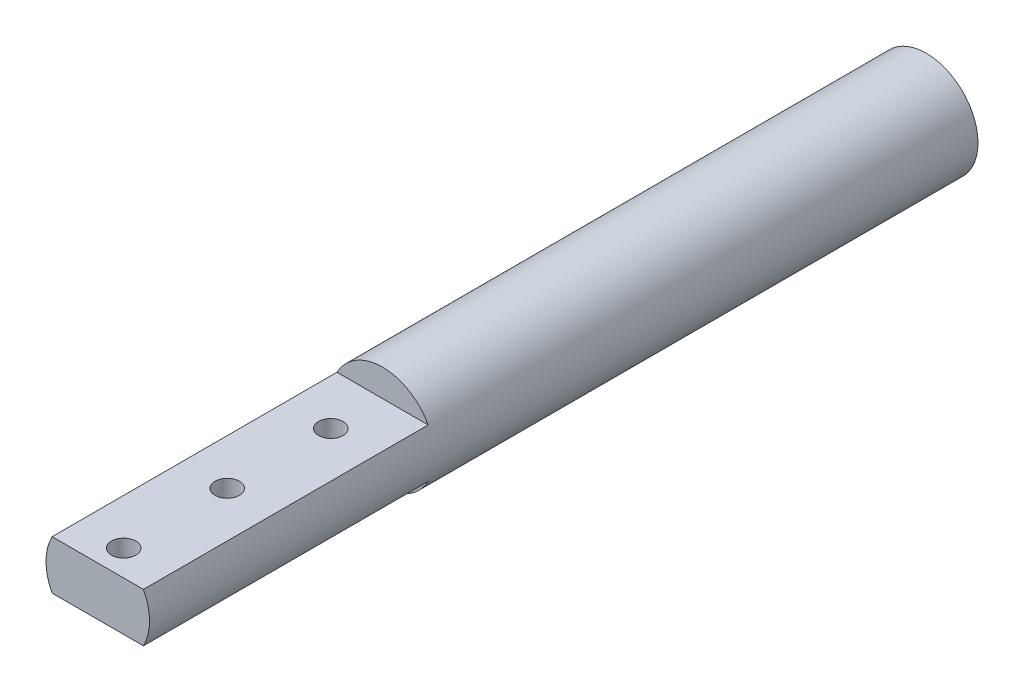
SolidWorks part; units mm, degrees
ref_plane "Front Plane" through (0, 0, 0) normal (0, 0, 1) x (1, 0, 0)
ref_plane "Top Plane" through (0, 0, 0) normal (0, 1, 0) x (1, 0, 0)
ref_plane "Right Plane" through (0, 0, 0) normal (1, 0, 0) x (0, 0, -1)
sketch "Sketch1" plane through (0, 0, 0) normal (0, 0, 1) x (1, 0, 0)
  circle A0 centre (0, 0) radius 6.35
  dimension "D1" = 12.7
extrude "Boss-Extrude1" add sketch "Sketch1" along normal mid plane 101.6
sketch "Sketch2" plane through (0, 0, 50.8) normal (0, 0, 1) x (1, 0, 0)
  line L0 (-5.5967, 3) -> (5.5967, 3)
  line L1 (-1000, 0) -> (49000, 0) construction
  line L2 (-5.5967, -3) -> (5.5967, -3)
  circle A0 centre (0, 0) radius 6.35 construction
  circle A1 centre (0, 0) radius 6.35
  circle M3 centre (0, 0) radius 6.35
  dimension "D1" = 3
extrude "Cut-Extrude1" cut sketch "Sketch2" against normal blind 34.925 contours L0 M3 | M3 region at (0, 4.3758, 50.8) region at (0, -4.3758, 50.8)
sketch "Sketch3" plane through (0, 3, 0) normal (0, 1, 0) x (1, 0, 0)
  line L1 (-5.5967, -50.8) -> (5.5967, -50.8) construction
  circle A0 centre (0, -22.225) radius 1.5
  circle A1 centre (0, -34.925) radius 1.5
  circle A2 centre (0, -47.625) radius 1.5
  point P8 (0, 0)
  point P9 (0, 0)
  point P10 (0, 0)
  point P11 (0, 0)
  point P12 (0, 0)
  point P13 (0, 0)
  point P14 (0, 0)
  dimension "D1" = 3
  dimension "D3" = 3.175
  dimension "D4" = 12.7
  dimension "D2" = 3
extrude "Cut-Extrude2" cut sketch "Sketch3" against normal up to next from surface starting at face at (0, 3, 33.3375)
